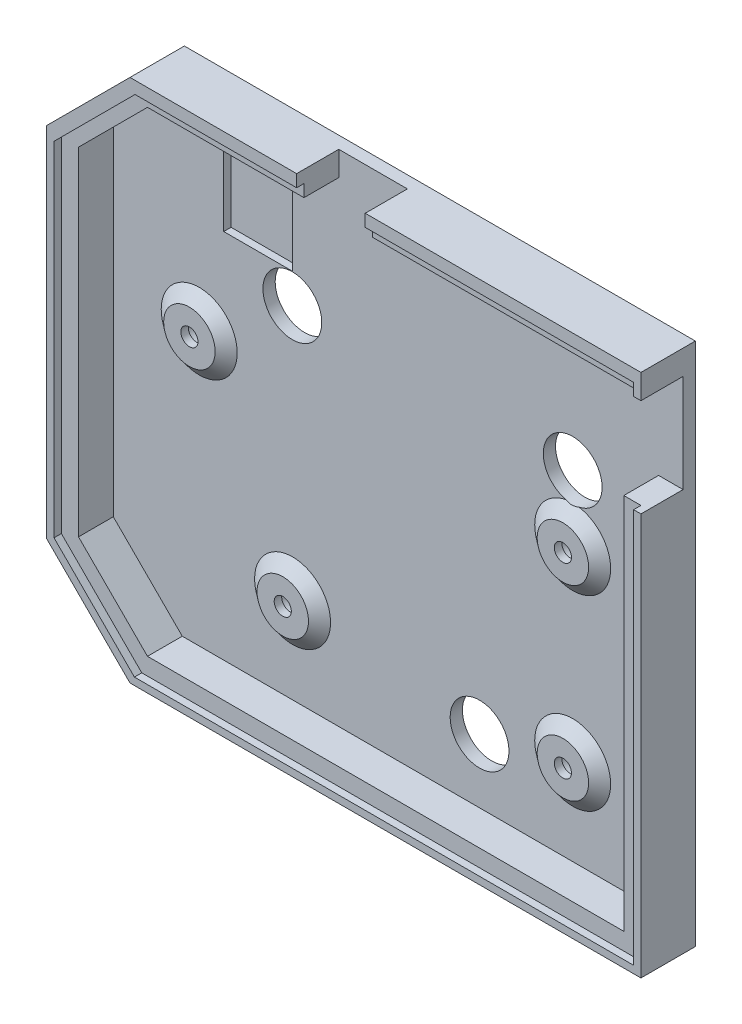
SolidWorks part; units mm, degrees
material "Delrin 2700 NC010, copolymère d'acétal à faible viscosité (SS)"
ref_plane "Plan de face" through (0, 0, 0) normal (0, 0, 1) x (1, 0, 0)
ref_plane "Plan de dessus" through (0, 0, 0) normal (0, 1, 0) x (1, 0, 0)
ref_plane "Plan de droite" through (0, 0, 0) normal (1, 0, 0) x (0, 0, -1)
sketch "Esquisse1" plane through (0, 0, 0) normal (0, 0, 1) x (1, 0, 0)
  line L0 (0, -85) -> (17, -102)
  line L4 (121.25, 5) -> (121.25, -102)
  line L5 (17, 5) -> (0, -12)
  line L7 (121.25, 5) -> (17, 5)
  line L8 (0, -12) -> (0, -85)
  line L9 (17, -102) -> (121.25, -102)
  dimension "D1" = 107
  dimension "D2" = 121.25
  dimension "D3" = 17
  dimension "D4" = 17
  dimension "D5" = 17
  dimension "D6" = 17
extrude "Boss.-Extru.1" add sketch "Esquisse1" along normal blind 2.5
sketch "Esquisse2" plane through (0, 0, 2.5) normal (0, 0, 1) x (1, 0, 0)
  line L0 (0, -12) -> (0, -85) construction
  line L1 (5, 0) -> (116.25, 0) construction
  line L2 (5, 0) -> (5, -97) construction
  line L3 (5, -97) -> (116.25, -97) construction
  line L4 (116.25, 0) -> (116.25, -97) construction
  line L5 (17, -102) -> (121.25, -102) construction
  line L6 (121.25, -102) -> (121.25, 5) construction
  line L7 (121.25, 5) -> (17, 5) construction
  line L8 (116.25, -20) -> (121.25, -20)
  line L9 (5, -82.9289) -> (19.0711, -97)
  line L10 (0, -85) -> (17, -102) construction
  line L11 (5, -14.0711) -> (19.0711, 0)
  line L12 (17, 5) -> (0, -12) construction
  line L14 (5, -14.0711) -> (5, -82.9289)
  line L15 (19.0711, -97) -> (116.25, -97)
  line L16 (121.25, 5) -> (121.25, -102) construction
  line L17 (121.25, -102) -> (17, -102)
  line L18 (17, -102) -> (0, -85)
  line L19 (0, -85) -> (0, -12)
  line L20 (0, -12) -> (17, 5)
  line L23 (116.25, -97) -> (116.25, -20)
  line L24 (121.25, -20) -> (121.25, -102)
  line L25 (51, 0) -> (51, 5)
  line L26 (65, 0) -> (65, 5)
  line L27 (19.0711, 0) -> (51, 0)
  line L28 (51, 5) -> (17, 5)
  line L29 (65, 5) -> (121.25, 5)
  line L32 (121.25, 0) -> (121.25, 5)
  line L33 (65, 0) -> (121.25, 0)
  point P33 (51, 0)
  point P34 (65, 0)
  dimension "D1" = 5
  dimension "D2" = 5
  dimension "D3" = 5
  dimension "D4" = 5
  dimension "D5" = 5
  dimension "D6" = 5
  dimension "D7" = 20
  dimension "D8" = 46
  dimension "D9" = 14
extrude "Boss.-Extru.2" add sketch "Esquisse2" along normal blind 8.6
sketch "Esquisse5" plane through (0, 0, 2.5) normal (0, 0, 1) x (1, 0, 0)
  line L0 (116.25, -97) -> (19.0711, -97) construction
  line L1 (116.25, -20) -> (116.25, -97) construction
  point P0 (22.525, -41.37)
  point P1 (98.725, -41.37)
  point P2 (98.725, -79.47)
  point P3 (41.575, -79.47)
  dimension "D1" = 38.1
  dimension "D2" = 17.53
  dimension "D3" = 17.525
  dimension "D4" = 76.2
  dimension "D5" = 57.15
ref_axis "Axe5" through (22.525, -41.37, 2.5) along (0, 0, 1)
ref_axis "Axe6" through (98.725, -41.37, 2.5) along (0, 0, 1)
ref_axis "Axe7" through (41.575, -79.47, 2.5) along (0, 0, 1)
ref_axis "Axe8" through (98.725, -79.47, 2.5) along (0, 0, 1)
sketch3d "Esquisse3D5"
  line L0 (22.525, -41.37, 2.5) -> (98.725, -41.37, 2.5) construction
  line L1 (41.575, -79.47, 2.5) -> (98.725, -79.47, 2.5) construction
ref_plane "Plan4" through (98.725, -41.37, 2.5) normal (1, 0, 0) x (0, 0, -1)
sketch "Esquisse8" plane through (98.725, -41.37, 2.5) normal (1, 0, 0) x (0, 0, -1)
  line L0 (0, 1.75) -> (0, 7.75)
  line L1 (0, 7.75) -> (-2, 5.25)
  line L2 (-2, 5.25) -> (-2, 1.75)
  line L3 (-2, 1.75) -> (0, 1.75)
  line L5 (0, 0) -> (-50.5083, 0) construction
  point P0 (0, 1.75)
  dimension "D1" = 6
  dimension "D2" = 3.5
  dimension "D3" = 2
  dimension "D4" = 1.75
revolve "Révolution3" add sketch "Esquisse8" angle 360 about axis through (98.725, -41.37, 2.5) along (0, 0, 1)
ref_plane "Plan5" through (41.575, -79.47, 2.5) normal (1, 0, 0) x (0, 0, -1)
sketch "Esquisse9" plane through (41.575, -79.47, 2.5) normal (1, 0, 0) x (0, 0, -1)
  line L0 (0, 1.75) -> (0, 7.75)
  line L1 (0, 7.75) -> (-2, 5.25)
  line L2 (-2, 5.25) -> (-2, 1.75)
  line L3 (-2, 1.75) -> (0, 1.75)
  point P0 (0, 1.75)
  dimension "D1" = 2
  dimension "D2" = 6
  dimension "D3" = 3.5
  dimension "D4" = 1.75
revolve "Révolution4" add sketch "Esquisse9" angle 360 about axis through (41.575, -79.47, 2.5) along (0, 0, 1)
ref_plane "Plan6" through (98.725, -79.47, 2.5) normal (1, 0, 0) x (0, 0, -1)
sketch "Esquisse10" plane through (98.725, -79.47, 2.5) normal (1, 0, 0) x (0, 0, -1)
  line L0 (0, 1.75) -> (0, 7.75)
  line L1 (0, 7.75) -> (-2, 5.25)
  line L2 (-2, 5.25) -> (-2, 1.75)
  line L3 (-2, 1.75) -> (0, 1.75)
  point P0 (0, 1.75)
  dimension "D1" = 6
  dimension "D2" = 2
  dimension "D3" = 3.5
  dimension "D4" = 1.75
revolve "Révolution5" add sketch "Esquisse10" angle 360 about axis through (98.725, -79.47, 2.5) along (0, 0, 1)
hole_wizard "Dégagement M32" positions "Esquisse15" profile "Esquisse16" hole size "M3" standard "Ansi Metric" end condition up to next
sketch "Esquisse15" plane through (0, 0, 2.5) normal (0, 0, 1) x (1, 0, 0)
  point P0 (22.525, -41.37)
  point P3 (41.575, -79.47)
  point P6 (98.725, -41.37)
  point P9 (98.725, -79.47)
sketch "Esquisse16" plane through (22.525, -41.37, 2.5) normal (1, 0, 0) x (0, -1, 0)
  line L0 (0, 0) -> (0, 2.5)
  line L1 (0, 2.5) -> (1.8, 2.5)
  line L2 (1.8, 2.5) -> (1.8, 0)
  line L5 (1.8, 0) -> (0, 0)
  line L11 (0, -6.35) -> (0, 107.95) construction
  dimension "Diamètre du perçage jusqu'au prochain" = 3.6
  dimension "Profondeur du perçage jusqu'au prochain" = 2.5
ref_plane "Plan7" through (22.525, -41.37, 2.5) normal (1, 0, 0) x (0, 0, -1)
sketch "Esquisse17" plane through (22.525, -41.37, 2.5) normal (1, 0, 0) x (0, 0, -1)
  line L1 (0, 1.75) -> (0, 7.75)
  line L2 (0, 7.75) -> (-2, 5.25)
  line L3 (-2, 5.25) -> (-2, 1.75)
  line L4 (-2, 1.75) -> (0, 1.75)
  line L5 (0, 0) -> (-51.036, 0) construction
  dimension "D1" = 1.75
  dimension "D2" = 6
  dimension "D3" = 3.5
  dimension "D4" = 2
revolve "Révolution6" add sketch "Esquisse17" angle 360 about axis through (22.525, -41.37, 2.5) along (0, 0, 1)
ref_point "Point1"
ref_point "Point2"
ref_point "Point3"
ref_point "Point4"
sketch "Esquisse18" plane through (0, 0, 0) normal (0, 0, -1) x (-1, 0, 0)
  circle A0 centre (-22.525, -41.37) radius 2.7
  circle A1 centre (-98.725, -41.37) radius 2.7
  circle A2 centre (-41.575, -79.47) radius 2.7
  circle A3 centre (-98.725, -79.47) radius 2.7
  dimension "D1" = 5.4
  dimension "D2" = 5.4
  dimension "D4" = 5.4
  dimension "D3" = 5.4
extrude "Enlèv. mat.-Extru.2" cut sketch "Esquisse18" against normal blind 3
sketch "Esquisse20" plane through (0, 0, 11.1) normal (0, 0, 1) x (1, 0, 0)
  line L1 (119.75, 2.5) -> (18.0355, 2.5)
  line L2 (-695.6105, 613.0147) -> (34659.7285, -34742.3244) construction
  line L3 (0, -85) -> (17, -102) construction
  line L4 (116.25, -97) -> (121.25, -102) construction
  line L12 (121.25, 5) -> (65, 5) construction
  line L13 (1.5, 2.5) -> (119.75, 2.5) construction
  line L14 (1.5, 2.5) -> (1.5, -100.5) construction
  line L15 (1.5, -100.5) -> (119.75, -100.5) construction
  line L16 (119.75, 2.5) -> (119.75, -100.5) construction
  line L17 (121.25, -20) -> (121.25, 0) construction
  line L18 (17, -102) -> (121.25, -102) construction
  line L19 (0, -12) -> (0, -85) construction
  line L25 (119.75, -100.5) -> (119.75, 2.5)
  line L26 (39.1913, 23.6558) -> (-16.7593, -32.2949) construction
  line L27 (17, 5) -> (0, -12) construction
  line L28 (18.0355, 2.5) -> (1.5, -14.0355)
  line L30 (1.5, -14.0355) -> (1.5, -84.0958)
  line L31 (1.5, -84.0958) -> (17.9042, -100.5)
  line L32 (17.9042, -100.5) -> (119.75, -100.5)
  dimension "D1" = 2.5
  dimension "D2" = 1.5
  dimension "D3" = 1.5
  dimension "D4" = 1.5
  dimension "D5" = 2.5
  dimension "D6" = 1.7
extrude "Enlèv. mat.-Extru.3" cut sketch "Esquisse20" against normal blind 1.5
sketch "Esquisse21" plane through (0, 0, 2.5) normal (0, 0, 1) x (1, 0, 0)
  circle A0 centre (98.725, -27.87) radius 6
  circle A1 centre (41.525, -27.37) radius 6
  circle A2 centre (79.725, -83.97) radius 6
  dimension "D1" = 13.5
  dimension "D2" = 14
  dimension "D4" = 19
  dimension "D3" = 19
  dimension "D5" = 4.5
extrude "Enlèv. mat.-Extru.4" cut sketch "Esquisse21" against normal blind 10 and the other way through all
chamfer "Chanfrein2" distance 1 angle 30 4 edges at (96.025, -79.47, 3) (38.875, -79.47, 3) (19.825, -41.37, 3) (96.025, -41.37, 3) first distance on face at (96.975, -79.47, 3) first distance on face at (39.825, -79.47, 3) first distance on face at (20.775, -41.37, 3) first distance on face at (96.975, -41.37, 3)
sketch "Esquisse22" plane through (0, 0, 2.5) normal (0, 0, 1) x (1, 0, 0)
  line L1 (27.525, -1.27) -> (41.525, -1.27)
  line L2 (27.525, -1.27) -> (27.525, -21.27)
  line L3 (27.525, -21.27) -> (41.525, -21.27)
  line L4 (41.525, -1.27) -> (41.525, -21.27)
  circle A0 centre (22.525, -41.37) radius 1.75 construction
  point P5 (22.525, -41.37)
  dimension "D1" = 20.1
  dimension "D2" = 5
  dimension "D3" = 14
  dimension "D4" = 20
extrude "Enlèv. mat.-Extru.13" cut sketch "Esquisse22" against normal blind 1.5 contours L2 L3 L4 L1
equation "\"r_ext\"= 5.4"
equation "\"D1@Esquisse18\"=\"r_ext\""
equation "\"D2@Esquisse18\"=\"r_ext\""
equation "\"D4@Esquisse18\"=\"r_ext\""
equation "\"D3@Esquisse18\"=\"r_ext\""
